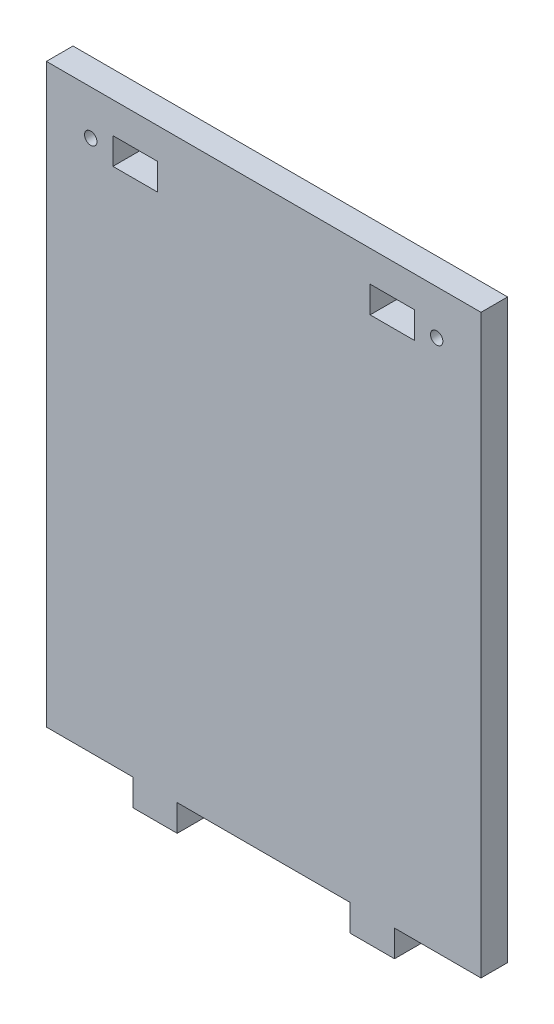
SolidWorks part; units mm, degrees
ref_plane "Plan de face" through (0, 0, 0) normal (0, 0, 1) x (1, 0, 0)
ref_plane "Plan de dessus" through (0, 0, 0) normal (0, 1, 0) x (1, 0, 0)
ref_plane "Plan de droite" through (0, 0, 0) normal (1, 0, 0) x (0, 0, -1)
sketch "Esquisse1" plane through (0, 0, 0) normal (0, 0, 1) x (1, 0, 0)
  line L0 (0, 176.8395) -> (0, -221.1538) construction
  line L1 (-49, 65) -> (49, 65)
  line L2 (-49, 65) -> (-49, -65)
  line L3 (-49, -65) -> (49, -65)
  line L4 (49, 65) -> (49, -65)
  line L5 (376.8436, 0) -> (-286.1998, 0) construction
  line L6 (-376.8436, 0) -> (286.1998, 0) construction
  line L7 (34, 58) -> (24, 58)
  line L8 (34, 58) -> (34, 52)
  line L9 (34, 52) -> (24, 52)
  line L10 (24, 58) -> (24, 52)
  line L11 (-24, 58) -> (-24, 52)
  line L12 (-34, 52) -> (-24, 52)
  line L13 (-34, 58) -> (-34, 52)
  line L14 (-34, 58) -> (-24, 58)
  dimension "D1" = 130
  dimension "D2" = 98
  dimension "D3" = 49
  dimension "D4" = 65
  dimension "D5" = 10
  dimension "D6" = 6
  dimension "D7" = 117
  dimension "D8" = 15
extrude "Boss.-Extru.1" add sketch "Esquisse1" along normal blind 6
sketch "Esquisse2" plane through (0, 0, 6) normal (0, 0, 1) x (1, 0, 0)
  line L1 (-49, -65) -> (49, -65) construction
  line L2 (29.5, -65) -> (19.5, -65)
  line L3 (29.5, -65) -> (29.5, -71)
  line L4 (29.5, -71) -> (19.5, -71)
  line L6 (154.6429, 0) -> (-167.6281, 0) construction
  line L7 (19.5, -65) -> (19.5, -71)
  line L8 (-49, 65) -> (-49, -65) construction
  line L9 (-19.5, -65) -> (-29.5, -65)
  line L10 (-19.5, -65) -> (-19.5, -71)
  line L11 (-19.5, -71) -> (-29.5, -71)
  line L12 (-29.5, -65) -> (-29.5, -71)
  dimension "D1" = 6
  dimension "D2" = 6
  dimension "D3" = 10
  dimension "D4" = 10
  dimension "D5" = 19.5
  dimension "D6" = 39
extrude "Boss.-Extru.2" add sketch "Esquisse2" against normal blind 6
sketch "Esquisse3" plane through (0, 0, 6) normal (0, 0, 1) x (1, 0, 0)
  line L0 (-34, 58) -> (-34, 52) construction
  line L2 (60.5882, 55) -> (-58.9143, 55) construction
  line L3 (34, 52) -> (34, 58) construction
  circle A0 centre (-39, 55) radius 1.4
  circle A3 centre (39, 55) radius 1.4
  dimension "D1" = 2.8
  dimension "D2" = 2.8
  dimension "D3" = 5
  dimension "D4" = 5
extrude "Enlèv. mat.-Extru.1" cut sketch "Esquisse3" against normal blind 6
equation "\"D3@Esquisse1\"=\"D2@Esquisse1\"/2"
equation "\"D4@Esquisse1\"=\"D1@Esquisse1\"/2"
